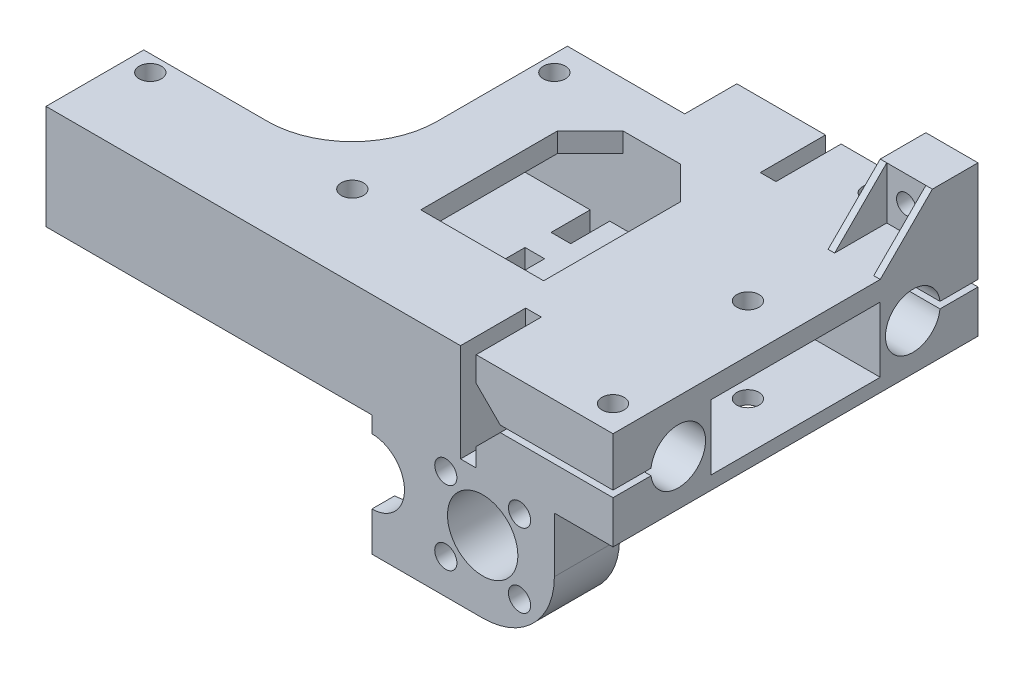
SolidWorks part; units mm, degrees
ref_plane "前视基准面" through (0, 0, 0) normal (0, 0, 1) x (1, 0, 0)
ref_plane "上视基准面" through (0, 0, 0) normal (0, 1, 0) x (1, 0, 0)
ref_plane "右视基准面" through (0, 0, 0) normal (1, 0, 0) x (0, 0, -1)
sketch "草图1" plane through (0, 0, 0) normal (0, 0, 1) x (1, 0, 0)
  line L0 (-21, 21) -> (21, -21) construction
  line L1 (-21, -21) -> (21, -21) construction
  line L2 (-21, -21) -> (-21, 21) construction
  line L3 (-21, 21) -> (21, 21) construction
  line L4 (-1001.4085, 24) -> (48998.5915, 24) construction
  line L5 (21, -21) -> (21, 21) construction
  line L6 (21, 21) -> (-21, -21) construction
  line L7 (11, 0) -> (11, 8.4569)
  line L8 (11, 8.4569) -> (21, 8.4569)
  line L9 (21, 8.4569) -> (21, 23.5)
  line L10 (21, 23.5) -> (-67, 23.5)
  line L11 (-67, 23.5) -> (-67, 7.5)
  line L12 (-67, 7.5) -> (-17, 7.5)
  line L13 (0, -11) -> (-17, -11)
  line L14 (-17, 7.5) -> (-17, 11)
  line L15 (-17, -11) -> (-17, 7.5)
  line L16 (11, 8.4569) -> (-4.5798, 8.4569)
  line L17 (21, 23.5) -> (28, 23.5)
  line L18 (21, 23.5) -> (21, 20.5)
  line L19 (21, 20.5) -> (28, 20.5)
  line L20 (28, 23.5) -> (28, 20.5)
  line L21 (21, 8.4569) -> (28, 8.4569)
  line L22 (21, 8.4569) -> (21, 10.5)
  line L23 (21, 10.5) -> (28, 10.5)
  line L24 (28, 8.4569) -> (28, 10.5)
  line L25 (12, 31.5) -> (20, 31.5)
  line L26 (12, 31.5) -> (12, 23.5)
  line L27 (12, 23.5) -> (21, 23.5)
  line L28 (20, 23.5) -> (20, 31.5)
  line L29 (-1067, 15.5) -> (48933, 15.5) construction
  circle A0 centre (0, 0) radius 5.4
  circle A1 centre (-17, 0) radius 4 construction
  circle A2 centre (-17, 0) radius 5
  circle A3 centre (-17, 0) radius 7.5
  circle A4 centre (-5.6569, 5.6569) radius 2.8 construction
  circle A5 centre (0, 0) radius 8 construction
  circle A6 centre (5.6569, 5.6569) radius 1.7
  circle A7 centre (5.6569, -5.6569) radius 1.7
  circle A8 centre (-5.6569, -5.6569) radius 1.7
  circle A9 centre (-5.6569, 5.6569) radius 1.7
  circle A10 centre (0, 0) radius 11
  circle A11 centre (-18.3322, 0) radius 11.0804
  circle A12 centre (16, 27.5) radius 1.5
  arc A13 (-4.5798, 8.4569) -> (-8.6437, 5.3766) centre (-5.6569, 5.6569) ccw
  point P0 (0, 0)
  point P25 (0, 0)
  point P54 (-67, 15.5)
  dimension "D1" = 10
  dimension "D2" = 10.8
  dimension "D3" = 15
  dimension "D4" = 5.6
  dimension "D5" = 16
  dimension "D6" = 3.4
  dimension "D9" = 22
  dimension "D10" = 16
  dimension "D11" = 10
  dimension "D18" = 3
  dimension "D21" = 3
  dimension "D8" = 3
  dimension "D12" = 5
  dimension "D13" = 5
  dimension "D14" = 7
  dimension "D15" = 50
  dimension "D16" = 8
  dimension "D17" = 8
  dimension "D19" = 4
  dimension "D20" = 4
  dimension "D22" = 1
  dimension "D7" = 4
extrude "凸台-拉伸1" add sketch "草图1" along normal blind 10 contours A11 A10 A0 A6 A7 A8 A9 | A10 A11 A3 | A10 A11 L14 A3 | L15 A11 A10 A3 | A11 L13 A10 | A11 A10 L7 L8 L9 L10 L11 L12 | L14 A11 L12 | L20 L17 L9 L19 | L21 L24 L23 L9 | A10 A11 | A10 L7 | A13 L16 A10 region at (9.8589, 6.4264, 0) region at (7.5793, -7.5793, 0) region at (-24.1727, 15.9599, 0) region at (-9.0499, -9.6181, 0) region at (0.0512, 9.4935, 0) region at (24.5, 9.4784, 0) region at (-13.2656, -7.8418, 0) region at (-8.7791, 0, 0) region at (-8.6998, 6.3406, 0) region at (-20.7478, 9.0153, 0) region at (-13.2656, 7.8418, 0) region at (24.5, 22, 0)
extrude "凸台-拉伸2" add sketch "草图1<6>" against normal blind 10 contours A11 A10 L16 L8 L9 L10 L11 L12 | L14 A11 L12 | A10 A11 L14 A3 | A10 A11 A3 | L15 A11 A10 A3 | A13 L16 A10 | A13 A10 A11 | L21 L24 L23 L9 | L18 L19 L20 L17 region at (-24.1727, 15.9599, 0) region at (0.0512, 9.4935, 0) region at (24.5, 9.4784, 0) region at (-13.2656, -7.8418, 0) region at (-8.7791, 0, 0) region at (-8.6998, 6.3406, 0) region at (-20.7478, 9.0153, 0) region at (-13.2656, 7.8418, 0)
sketch "草图1<6>" plane through (0, 0, 0) normal (0, 0, 1) x (1, 0, 0) same geometry as "草图1"
sketch "草图3" plane through (0, 0, 0) normal (0, 0, -1) x (-1, 0, 0)
  line L0 (0, 0) -> (5.6569, 5.6569) construction
  line L1 (7.9196, 3.3941) -> (8.7478, 6.4851)
  line L2 (8.7478, 6.4851) -> (6.4851, 8.7478)
  line L3 (6.4851, 8.7478) -> (3.3941, 7.9196)
  line L4 (3.3941, 7.9196) -> (2.5659, 4.8286)
  line L5 (2.5659, 4.8286) -> (4.8286, 2.5659)
  line L6 (4.8286, 2.5659) -> (7.9196, 3.3941)
  line L8 (-2.5659, 4.8286) -> (-3.3941, 7.9196)
  line L9 (-3.3941, 7.9196) -> (-6.4851, 8.7478)
  line L10 (-6.4851, 8.7478) -> (-8.7478, 6.4851)
  line L11 (-8.7478, 6.4851) -> (-7.9196, 3.3941)
  line L12 (-7.9196, 3.3941) -> (-4.8286, 2.5659)
  line L13 (-4.8286, 2.5659) -> (-2.5659, 4.8286)
  line L14 (-3.3941, -7.9196) -> (-2.5659, -4.8286)
  line L15 (-2.5659, -4.8286) -> (-4.8286, -2.5659)
  line L16 (-4.8286, -2.5659) -> (-7.9196, -3.3941)
  line L17 (-7.9196, -3.3941) -> (-8.7478, -6.4851)
  line L18 (-8.7478, -6.4851) -> (-6.4851, -8.7478)
  line L19 (-6.4851, -8.7478) -> (-3.3941, -7.9196)
  line L20 (2.5659, -4.8286) -> (3.3941, -7.9196)
  line L21 (3.3941, -7.9196) -> (6.4851, -8.7478)
  line L22 (6.4851, -8.7478) -> (8.7478, -6.4851)
  line L23 (8.7478, -6.4851) -> (7.9196, -3.3941)
  line L24 (7.9196, -3.3941) -> (4.8286, -2.5659)
  line L25 (4.8286, -2.5659) -> (2.5659, -4.8286)
  circle A0 centre (5.6569, 5.6569) radius 2.7713 construction
  circle A2 centre (-5.6569, 5.6569) radius 2.7713 construction
  circle A3 centre (-5.6569, -5.6569) radius 2.7713 construction
  circle A4 centre (5.6569, -5.6569) radius 2.7713 construction
  dimension "D1" = 3.2
  dimension "D2" = 3.2
  dimension "D3" = 3.2
  dimension "D4" = 3.2
extrude "切除-拉伸1" cut sketch "草图3" against normal blind 2
extrude "凸台-拉伸3" add sketch "草图1<7>" against normal blind 36 from offset 10 contours A11 A10 L16 L8 L9 L10 L11 L12 | L14 A11 L12 | A10 A11 L14 A3 | A10 A11 A3 | L15 A11 A10 A3 | A13 L16 A10 | A13 A10 A11 region at (-24.1727, 15.9599, 0) region at (0.0512, 9.4935, 0) region at (-13.2656, -7.8418, 0) region at (-8.7791, 0, 0) region at (-8.6998, 6.3406, 0) region at (-20.7478, 9.0153, 0) region at (-13.2656, 7.8418, 0) offset against normal yes
sketch "草图1<7>" plane through (0, 0, 0) normal (0, 0, 1) x (1, 0, 0) same geometry as "草图1"
extrude "凸台-拉伸4" add sketch "草图1<8>" along normal blind 3.5 from offset 6.5 contours A10 A3 L15 A2 | A3 A10 region at (-16.8361, -6.25, 0) region at (-10.2789, 0, 0)
sketch "草图1<8>" plane through (0, 0, 0) normal (0, 0, 1) x (1, 0, 0) same geometry as "草图1"
extrude "凸台-拉伸5" add sketch "草图1<9>" along normal blind 4 from offset 46 contours A10 A3 L15 A2 | A3 A10 region at (-16.8361, -6.25, 0) region at (-10.2789, 0, 0) offset against normal yes
sketch "草图1<9>" plane through (0, 0, 0) normal (0, 0, 1) x (1, 0, 0) same geometry as "草图1"
extrude "凸台-拉伸6" add sketch "草图1<10>" along normal blind 7 from offset 46 contours L25 L26 L10 A12 region at (16, 23.6131, 0) offset against normal yes
sketch "草图1<10>" plane through (0, 0, 0) normal (0, 0, 1) x (1, 0, 0) same geometry as "草图1"
sketch "草图4" plane through (20, 0, 0) normal (1, 0, 0) x (0, 0, -1)
  line L0 (39, 31.5) -> (31, 23.5)
  line L1 (46, 23.5) -> (10, 23.5) construction
rib "筋2" sketch "草图4" sketch "草图4" thickness 1 extrusion direction parallel to sketch draft on no parameters "D1"=1
sketch "草图5" plane through (12, 0, 0) normal (-1, 0, 0) x (0, 0, 1)
  line L0 (-39, 31.5) -> (-31, 23.5) construction
  line L1 (-39, 31.5) -> (-31, 23.5)
rib "筋3" sketch "草图5" sketch "草图5" thickness 1 extrusion direction parallel to sketch draft on no parameters "D1"=1
sketch "草图6" plane through (0, 0, -39) normal (0, 0, 1) x (1, 0, 0)
  circle A0 centre (16, 27.5) radius 1.5 construction
  circle A1 centre (16, 27.5) radius 1.5
extrude "凸台-拉伸7" add sketch "草图6" against normal blind 0.4
sketch "草图7" plane through (0, 23.5, 0) normal (0, 1, 0) x (1, 0, 0)
  line L0 (-987.3, 18) -> (49012.7, 18) construction
  line L1 (-8.6437, 5) -> (-5.6437, 5)
  line L2 (-8.6437, 5) -> (-8.6437, 11)
  line L3 (-8.6437, 11) -> (-5.6437, 11)
  line L4 (-5.6437, 5) -> (-5.6437, 11)
  line L5 (-5.6437, 31) -> (-5.6437, 25)
  line L6 (-8.6437, 15) -> (-5.6437, 15)
  line L7 (-8.6437, 15) -> (-8.6437, 21)
  line L8 (-8.6437, 21) -> (-5.6437, 21)
  line L9 (-5.6437, 15) -> (-5.6437, 21)
  line L10 (-8.6437, 31) -> (-8.6437, 25)
  line L11 (-8.6437, 31) -> (-5.6437, 31)
  line L12 (-8.6437, 25) -> (-5.6437, 25)
  line L13 (-8.6437, 46) -> (-8.6437, 0) construction
  line L14 (-24.5, 5) -> (-21.5, 5)
  line L15 (-24.5, 5) -> (-24.5, 11)
  line L16 (-24.5, 11) -> (-21.5, 11)
  line L17 (-21.5, 5) -> (-21.5, 11)
  line L18 (-21.5, 31) -> (-21.5, 25)
  line L19 (-24.5, 15) -> (-21.5, 15)
  line L20 (-24.5, 15) -> (-24.5, 21)
  line L21 (-24.5, 21) -> (-21.5, 21)
  line L22 (-21.5, 15) -> (-21.5, 21)
  line L23 (-24.5, 31) -> (-24.5, 25)
  line L24 (-24.5, 31) -> (-21.5, 31)
  line L25 (-24.5, 25) -> (-21.5, 25)
  line L26 (-24.5, -10) -> (-9.5, -10) construction
  line L27 (-24.5, 5) -> (-5.6437, 5)
  line L28 (-24.5, 5) -> (-24.5, 31)
  line L29 (-24.5, 31) -> (-5.6437, 31)
  line L30 (-5.6437, 5) -> (-5.6437, 31)
  line L31 (28, 0) -> (0, 0) construction
  line L32 (-27, 39) -> (-69, 39) construction
  line L33 (-27, 39) -> (-27, -3) construction
  line L34 (-27, -3) -> (-69, -3) construction
  line L35 (-69, 39) -> (-69, -3) construction
  line L36 (-27, 39) -> (-69, -3) construction
  line L37 (-27, -3) -> (-69, 39) construction
  line L38 (28, -10) -> (28, 10) construction
  line L39 (-17, 46) -> (-17, 38)
  line L40 (-48, 5) -> (-69, 5)
  line L41 (-35, 18) -> (-35, 38)
  line L42 (-69, 5) -> (-69, 46)
  line L43 (-69, 46) -> (-17, 46)
  line L44 (-67, 46) -> (-17, 46) construction
  line L45 (-17, 38) -> (-35, 38)
  line L46 (21, 46) -> (-4.5798, 46) construction
  line L47 (-1, 46) -> (-3.4, 46)
  line L48 (-1, 46) -> (-1, 36)
  line L49 (-1, 36) -> (-3.4, 36)
  line L50 (-3.4, 46) -> (-3.4, 36)
  line L51 (-1, -10) -> (-3.4, -10)
  line L52 (-1, -10) -> (-1, 0)
  line L53 (-3.4, -10) -> (-3.4, 0)
  line L54 (-1, 0) -> (-3.4, 0)
  circle A0 centre (12.7, 18) radius 1.7
  circle A1 centre (16, -6) radius 1.7
  circle A2 centre (8, 42) radius 1.7
  circle A3 centre (-48, 18) radius 13
  circle A4 centre (-32.5, 2.5) radius 1.7
  circle A5 centre (-63.5, 2.5) radius 1.7
  circle A6 centre (-63.5, 33.5) radius 1.7
  circle A7 centre (-32.5, 33.5) radius 1.7
  circle A8 centre (24.5, -5) radius 1.35
  circle A9 centre (24.5, 5) radius 1.35
  point P36 (-48, 18)
  point P59 (-48, 18)
  line M27 (12, 46) -> (-67, 46)
  line M28 (-67, 46) -> (-67, -10)
  line M29 (-67, -10) -> (28, -10)
  dimension "D1" = 3.4
  dimension "D9" = 3.4
  dimension "D12" = 3.4
  dimension "D18" = 26
  dimension "D19" = 3.4
  dimension "D22" = 2.7
  dimension "D2" = 18
  dimension "D3" = 12.7
  dimension "D4" = 3
  dimension "D5" = 6
  dimension "D6" = 6
  dimension "D8" = 24.5
  dimension "D10" = 42
  dimension "D11" = 8
  dimension "D13" = 6
  dimension "D14" = 16
  dimension "D16" = 42
  dimension "D17" = 15.5
  dimension "D21" = 15
  dimension "D23" = 10
  dimension "D24" = 24.5
  dimension "D25" = 4.5
  dimension "D26" = 2.4
  dimension "D27" = 1
  dimension "D28" = 18
  dimension "D29" = 8.6437
  dimension "D30" = 26
  dimension "D31" = 17
  dimension "D32" = 48
  dimension "D7" = 2
  dimension "D20" = 4
extrude "切除-拉伸2" cut sketch "草图7" against normal through all contours A3 L41 L40 A6 M27 M28 | A3 | A6 | A4 | A7 | A8 | A0 | A2 | A5 | A1 | A9 region at (-49.1293, 23.5, -33.3701) region at (-48, 23.5, -18) region at (12.7, 23.5, -18) region at (8, 23.5, -42) region at (-32.5, 23.5, -2.5) region at (-63.5, 23.5, -33.5) region at (-32.5, 23.5, -33.5) region at (24.5, 23.5, 5)
sketch "草图8" plane through (21, 0, 0) normal (1, 0, 0) x (0, 0, -1)
  line L0 (-1024.2568, 15.5) -> (48975.7432, 15.5) construction
  line L1 (-10, 10.5) -> (-10, 20.5) construction
  line L2 (18, -1011) -> (18, 48989) construction
  line L3 (0, 19.7) -> (0, 11.3)
  line L5 (5, 10.5) -> (31, 10.5)
  line L6 (5, 10.5) -> (5, 20.5)
  line L7 (5, 20.5) -> (31, 20.5)
  line L8 (31, 10.5) -> (31, 20.5)
  line L9 (5, 10.5) -> (31, 20.5) construction
  line L10 (5, 20.5) -> (31, 10.5) construction
  line L11 (-4.1701, 16) -> (-10, 16)
  line L12 (-4.1701, 15) -> (-10, 15)
  line L13 (40.1701, 15) -> (46, 15)
  line L14 (40.1701, 16) -> (46, 16)
  line L15 (36, 19.7) -> (36, 11.3)
  line L17 (-10, 16) -> (-10, 15)
  line L18 (46, 16) -> (46, 15)
  circle A0 centre (0, 15.5) radius 4.2
  circle A1 centre (36, 15.5) radius 4.2
  point P2 (18, 15.5)
  line M5 (-10, 20.5) -> (-10, 10.5)
  line M9 (46, 8.4569) -> (46, 23.5)
  dimension "D6" = 8.4
  dimension "D7" = 36
  dimension "D1" = 18
  dimension "D2" = 26
  dimension "D3" = 10
  dimension "D4" = 15.5
  dimension "D5" = 8
  dimension "D8" = 1
extrude "切除-拉伸3" cut sketch "草图8" against normal through all contours L5 L8 L7 L6 region at (21, 15.5, -18)
extrude "切除-拉伸4" cut sketch "草图8<3>" against normal blind 22 contours A1 L15 | L3 A0 region at (21, 15.5, -1.7825) region at (21, 15.5, -34.2175)
sketch "草图8<3>" plane through (21, 0, 0) normal (1, 0, 0) x (0, 0, -1) same geometry as "草图8"
extrude "切除-拉伸5" cut sketch "草图8<4>" against normal blind 24 contours A1 L15 | L14 A1 L13 M9 | L3 A0 | A0 L11 L12 M5 region at (21, 15.5, 1.7825) region at (21, 15.5, 7.095) region at (21, 15.5, -43.095) region at (21, 15.5, -37.7825)
sketch "草图8<4>" plane through (21, 0, 0) normal (1, 0, 0) x (0, 0, -1) same geometry as "草图8"
extrude "切除-拉伸9" cut sketch "草图7<4>" against normal blind 15.05 contours L52 L54 L53 M29 | L48 L49 L50 L47 region at (-2.2, 23.5, 5)
sketch "草图7<4>" plane through (0, 23.5, 0) normal (0, 1, 0) x (1, 0, 0) same geometry as "草图7"
chamfer "倒角1" distance 3.7 angle 45 4 edges at (-1, 16, -43.0851) (-1, 15, -43.0851) (-1, 16, 7.0851) (-1, 15, 7.0851)
extrude "切除-拉伸10" cut sketch "草图7<5>" against normal up to vertex (18.1234 mm away) contours L6 L9 L8 L7 | L10 L12 L5 L11 | L23 L25 L18 L24 | L19 L22 L21 L20 | L14 L17 L16 L15 | L4 L3 L2 L1 region at (-23, 23.5, -8) region at (-7.1437, 23.5, -18) region at (-23, 23.5, -18) region at (-7.1437, 23.5, -28) region at (-23, 23.5, -28) up to point (-8.6437, 5.3766, -46)
sketch "草图7<5>" plane through (0, 23.5, 0) normal (0, 1, 0) x (1, 0, 0) same geometry as "草图7"
extrude "切除-拉伸11" cut sketch "草图7<6>" against normal up to next contours L3 L30 L6 L7 L8 L12 L10 L29 L18 L25 L28 L21 L22 L19 L16 L17 L27 L2 region at (-15.0719, 23.5, -18)
sketch "草图7<6>" plane through (0, 23.5, 0) normal (0, 1, 0) x (1, 0, 0) same geometry as "草图7"
chamfer "倒角2" distance 5 2 edges at (-24.5, 22, -31) (-5.6437, 22, -31)
chamfer "倒角3" distance 2 distance2 2.5 1 edges at (-12, 0, -42) first distance on face at (-13.875, 0, -42)
sketch "草图9" plane through (0, 0, 10) normal (0, 0, 1) x (1, 0, 0)
  line L0 (20, 31.5) -> (20, 7.2174)
  line L1 (20, 7.2174) -> (31.3229, 7.2174)
  line L2 (31.3229, 7.2174) -> (31.3229, 31.5)
  line L3 (31.3229, 31.5) -> (20, 31.5)
extrude "切除-拉伸12" cut sketch "草图9" against normal through all
extrude "切除-拉伸13" cut sketch "草图1<14>" against normal blind 10 from vertex contours A12 region at (16, 27.5, 0) starting at point (13, 31.5, -39)
sketch "草图1<14>" plane through (0, 0, 0) normal (0, 0, 1) x (1, 0, 0) same geometry as "草图1"
